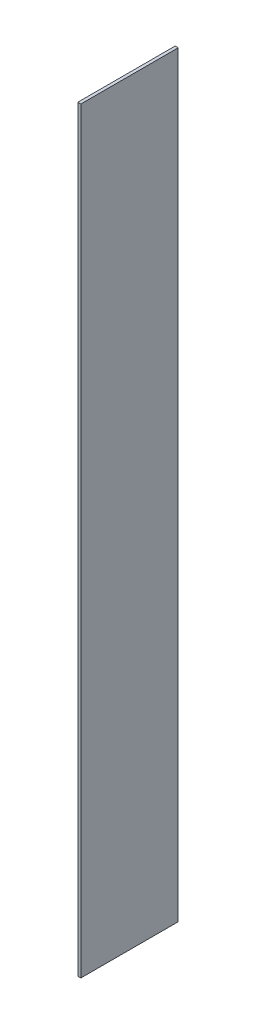
SolidWorks part; units mm, degrees
ref_plane "Top" through (0, 0, 0) normal (0, 0, 1) x (1, 0, 0)
ref_plane "Front" through (0, 0, 0) normal (0, 1, 0) x (1, 0, 0)
ref_plane "Right" through (0, 0, 0) normal (1, 0, 0) x (0, 0, -1)
sketch "Profile Sketch" plane through (0.0456, 0, -0.0242) normal (0, 1, 0) x (-1, 0, 0)
  line L0 (0.5956, -17.4758) -> (0.5956, 0.0242)
  line L1 (0.5956, 0.0242) -> (0.0456, 0.0242)
  line L2 (0.0456, 0.0242) -> (0.0456, -17.4758)
  line L3 (0.0456, -17.4758) -> (0.5956, -17.4758)
  dimension "D1" = 17.5
  dimension "D2" = 0.55
extrude "Profile Extrude" add sketch "Profile Sketch" along normal blind 136
ref_plane "Mid Plane" through (0, 68, 0) normal (0, -1, 0) x (-1, 0, 0)
